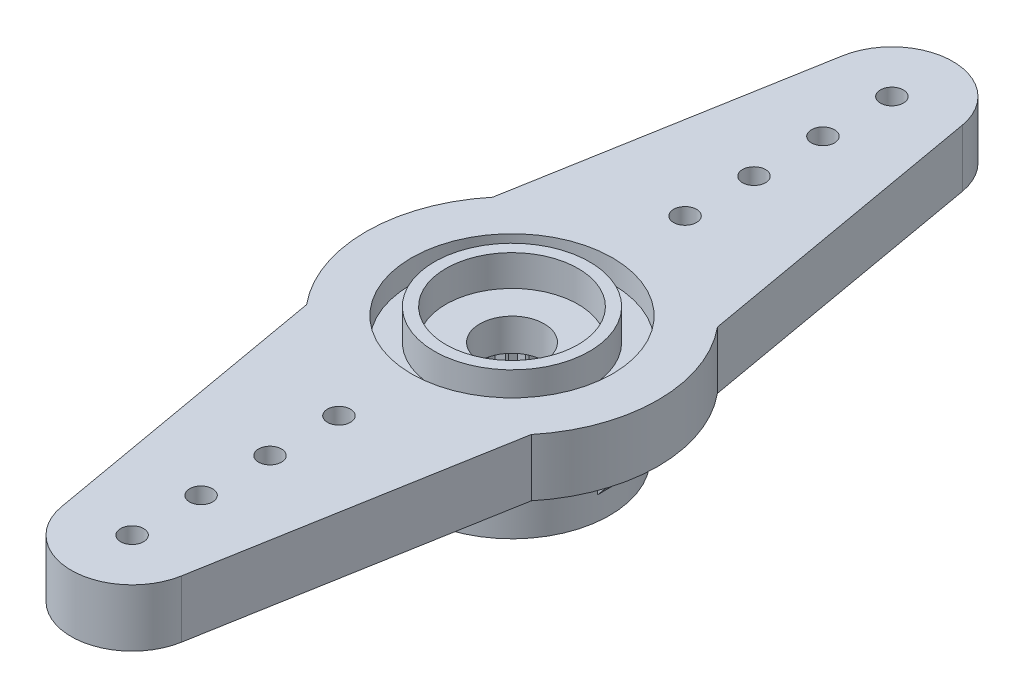
SolidWorks part; units mm, degrees
material "PC High Viscosity"
ref_plane "Front Plane" through (0, 0, 0) normal (0, 0, 1) x (1, 0, 0)
ref_plane "Top Plane" through (0, 0, 0) normal (0, 1, 0) x (1, 0, 0)
ref_plane "Right Plane" through (0, 0, 0) normal (1, 0, 0) x (0, 0, -1)
sketch "BaseS" plane through (0, 0, 0) normal (0, 1, 0) x (1, 0, 0)
  circle A0 centre (0, 0) radius 6.35
  dimension "D1" = 12.7
extrude "BASE" add sketch "BaseS" along normal blind 5.4
sketch "TopBoreS" plane through (0, 5.4, 0) normal (0, 1, 0) x (1, 0, 0)
  circle A0 centre (0, 0) radius 1.4
  dimension "D1" = 2.8
extrude "TOP BORE" cut sketch "TopBoreS" against normal through all
sketch "HornHalfS" plane through (0, 5.4, 0) normal (0, 1, 0) x (1, 0, 0)
  line L0 (0, 0) -> (0, 16.53) construction
  line L1 (-2.6097, 16.9902) -> (-4.8916, 4.049)
  line L2 (0, 19.18) -> (0, 16.53) construction
  line L3 (2.6097, 16.9902) -> (4.8916, 4.049)
  arc A0 (2.6097, 16.9902) -> (-2.6097, 16.9902) centre (0, 16.53) ccw
  arc A1 (4.8916, 4.049) -> (-4.8916, 4.049) centre (0, 0) ccw
  circle A2 centre (0, 0) radius 6.35 construction
  dimension "D1" = 5.3
  dimension "D2" = 19.18
  dimension "D3" = 10
  dimension "D4" = 9.7832
extrude "HORN HALF" add sketch "HornHalfS" against normal blind 2.5
sketch "HornAttachS" plane through (0, 5.4, 0) normal (0, 1, 0) x (1, 0, 0)
  circle A0 centre (0, 16.53) radius 0.5
  dimension "D1" = 1
extrude "HORN ATTACH" cut sketch "HornAttachS" against normal through all
sketch "HA LP RS" plane through (0, 0, 0) normal (0, 1, 0) x (1, 0, 0)
  line L0 (0, 0) -> (0, 16.53) construction
pattern_linear "HA LP" count 4 spacing 3 along (0, 0, 1) of "HORN ATTACH"
mirror "HORN BODIES" about plane through (0, 0, 0) normal (0, 0, 1) of "HA LP", "HORN ATTACH", "HORN HALF"
sketch "ToothS" plane through (0, 0, 0) normal (0, -1, 0) x (1, 0, 0)
  line L0 (0, -2.9) -> (0.2629, -2.5867)
  line L1 (0, -2.9) -> (-0.2629, -2.5867)
  line L2 (0, -2.6) -> (0, -2.9) construction
  line L3 (0, 0) -> (0, -2.6) construction
  arc A0 (-0.2629, -2.5867) -> (0.2629, -2.5867) centre (0, 0) ccw
  dimension "D1" = 5.2
  dimension "D2" = 80
  dimension "D3" = 0.3
extrude "TOOTH" cut sketch "ToothS" against normal blind 3
pattern_circular "TOOTH CP" count 26 over 360 about axis through (0, 5.4, 0) along (0, -1, 0) of "TOOTH"
sketch "BottomBoreS" plane through (0, 0, 0) normal (0, -1, 0) x (-1, 0, 0)
  circle A0 centre (0, 0) radius 2.6
  arc A1 (0.2629, 2.5867) -> (-0.2629, 2.5867) centre (0, 0) ccw construction
extrude "BOTTOM BORE" cut sketch "BottomBoreS" against normal up to surface (3 mm away) up to face at (-0.6451, 3, 2.6172)
sketch "HoldingShaftS" plane through (0, 0, 0) normal (0, -1, 0) x (1, 0, 0)
  circle A0 centre (0, 0) radius 6.35 construction
  circle A1 centre (0, 0) radius 6.35
  circle A2 centre (0, 0) radius 4.25
  dimension "D1" = 2.1
  dimension "D2" = 8.5
extrude "HOLDING SHAFT" cut sketch "HoldingShaftS" against normal up to surface (2.9 mm away) up to face at (0, 2.9, -13.03)
sketch "RibS" plane through (0, 0, 0) normal (0, 0, 1) x (1, 0, 0)
  line L0 (4.21, 1) -> (5.8043, 2.9)
  line L1 (5.8043, 2.9) -> (4.21, 2.9)
  line L2 (4.21, 1) -> (4.16, 1)
  line L3 (4.16, 1) -> (4.16, 2.9)
  line L4 (4.21, 1) -> (4.21, 2.9) construction
  line L5 (4.16, 2.9) -> (4.21, 2.9)
  line L6 (-4.25, 2.9) -> (4.25, 2.9) construction
  line L7 (4.21, 2.9) -> (4.25, 2.9) construction
  line L8 (4.25, 0) -> (4.25, 2.9) construction
  dimension "D1" = 1.9
  dimension "D2" = 0.05
  dimension "D3" = 40
  dimension "D4" = 0.09
extrude "RIB" add sketch "RibS" along normal mid plane 1
pattern_circular "RIB CP" count 4 over 360 about axis through (0, 20.8605, 0) along (0, -1, 0) of "RIB"
sketch "TopCutS" plane through (0, 5.4, 0) normal (0, 1, 0) x (1, 0, 0)
  circle A0 centre (0, 0) radius 4.375
  arc A1 (4.8916, -4.049) -> (4.8916, 4.049) centre (0, 0) ccw construction
  dimension "D1" = 1.975
  dimension "D2" = 8.75
extrude "TOP CUT" cut sketch "TopCutS" against normal blind 1
sketch "TopPocketCylinderS" plane through (0, 4.4, 0) normal (0, 1, 0) x (1, 0, 0)
  circle A0 centre (0, 0) radius 2.875
  circle A1 centre (0, 0) radius 3.375
  circle A2 centre (0, 0) radius 4.375 construction
  dimension "D2" = 0.5
  dimension "D1" = 1
  dimension "D3" = 6.75
extrude "TOP POCKET CYLINDER" add sketch "TopPocketCylinderS" along normal offset from surface (1.35 mm away) 0.35 up to face at (0, 5.4, 4.375) offset beyond the face yes
ref_point "Point1"
ref_point "Point2"
ref_axis "Axis1" through (0, 5.4, -16.53) along (0, 0, 1)
